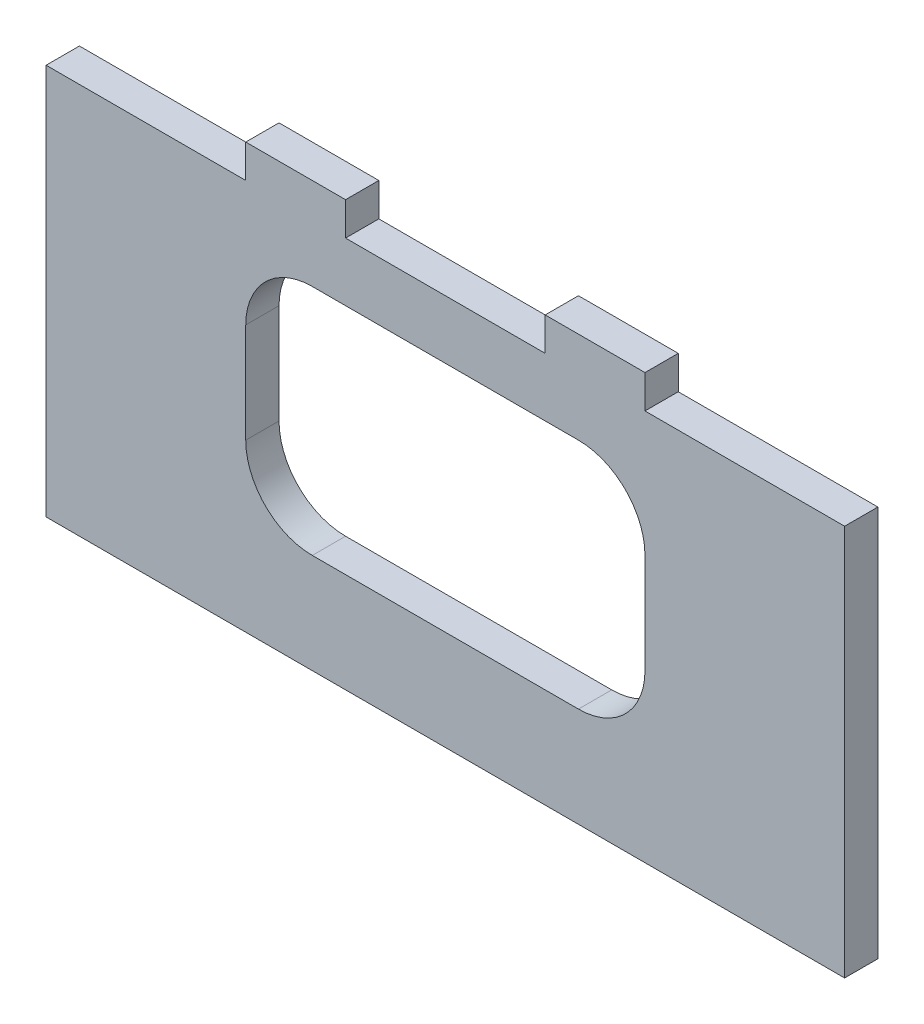
SolidWorks part; units mm, degrees
ref_plane "Ebene vorne" through (0, 0, 0) normal (0, 0, 1) x (1, 0, 0)
ref_plane "Ebene oben" through (0, 0, 0) normal (0, 1, 0) x (1, 0, 0)
ref_plane "Ebene rechts" through (0, 0, 0) normal (1, 0, 0) x (0, 0, -1)
sketch "Skizze1" plane through (0, 0, 0) normal (0, 0, 1) x (1, 0, 0)
  line L1 (0, 0) -> (120, 0)
  line L2 (0, 0) -> (0, 58.8)
  line L3 (0, 58.8) -> (120, 58.8)
  line L4 (120, 0) -> (120, 58.8)
  dimension "D1" = 120
  dimension "D2" = 58.8
extrude "Aufsatz-Linear austragen1" add sketch "Skizze1" along normal blind 5
sketch "Skizze2" plane through (0, 0, 5) normal (0, 0, 1) x (1, 0, 0)
  line L0 (60, 58.8) -> (60, 50) construction
  line L1 (30, 50) -> (90, 50)
  line L2 (30, 50) -> (30, 15)
  line L3 (30, 15) -> (90, 15)
  line L4 (90, 50) -> (90, 15)
  line L5 (120, 58.8) -> (0, 58.8) construction
  line L6 (60, 50) -> (60, 15) construction
  line L7 (60, 15) -> (60, 0) construction
  line L8 (0, 0) -> (120, 0) construction
  dimension "D1" = 35
  dimension "D2" = 60
  dimension "D3" = 15
extrude "Schnitt-Linear austragen1" cut sketch "Skizze2" against normal through all
fillet "Verrundung1" radius 10 4 edges at (30, 15, 2.5) (90, 15, 2.5) (90, 50, 2.5) (30, 50, 2.5)
sketch "Skizze3" plane through (0, 58.8, 0) normal (0, 1, 0) x (1, 0, 0)
  line L0 (60, 0) -> (60, -5) construction
  line L5 (120, 0) -> (0, 0) construction
  line L6 (120, -5) -> (0, -5) construction
  line L7 (75, 0) -> (75, -5)
  line L8 (30, 0) -> (45, 0)
  line L9 (30, 0) -> (30, -5)
  line L10 (30, -5) -> (45, -5)
  line L11 (45, 0) -> (45, -5)
  line L12 (90, -5) -> (75, -5)
  line L13 (90, 0) -> (90, -5)
  line L14 (90, 0) -> (75, 0)
  dimension "D1" = 15
  dimension "D2" = 30
extrude "Aufsatz-Linear austragen2" add sketch "Skizze3" along normal blind 5
